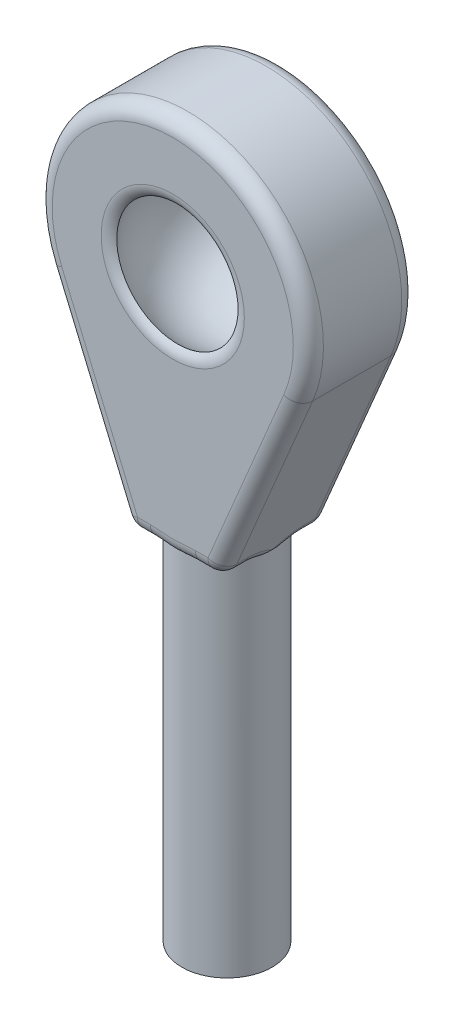
SolidWorks part; units mm, degrees
ref_plane "Front Plane" through (0, 0, 0) normal (0, 0, 1) x (1, 0, 0)
ref_plane "Top Plane" through (0, 0, 0) normal (0, 1, 0) x (1, 0, 0)
ref_plane "Right Plane" through (0, 0, 0) normal (1, 0, 0) x (0, 0, -1)
sketch "Sketch1" plane through (0, 0, 0) normal (0, 1, 0) x (1, 0, 0)
  circle A0 centre (0, 0) radius 1.5
  dimension "D1" = 3
extrude "Boss-Extrude1" add sketch "Sketch1" along normal blind 12
cosmetic thread "Cosmetic Thread1" parameters "D2"=2
sketch "Sketch3" plane through (0, 0, 0) normal (1, 0, 0) x (0, 0, -1)
  line L1 (-2.2, 21.3856) -> (2.2, 21.3856) construction
  line L2 (-2.2, 21.3856) -> (-2.2, 18.6144) construction
  line L3 (-2.2, 18.6144) -> (2.2, 18.6144) construction
  line L4 (2.2, 21.3856) -> (2.2, 18.6144) construction
  line L5 (-2.2, 21.3856) -> (2.2, 18.6144) construction
  line L6 (-2.2, 18.6144) -> (2.2, 21.3856) construction
  circle A0 centre (0, 20) radius 2.6
  point P0 (0, 20)
  point P8 (-1.8, 21.8762)
  dimension "D2" = 5.2
  dimension "D1" = 4.4
  dimension "D3" = 20
  dimension "D4" = 1.8
sketch "Sketch2" plane through (0, 0, 0) normal (0, 0, 1) x (1, 0, 0)
  line L0 (1.5, 12) -> (4.144, 18.2457)
  line L1 (-1.5, 12) -> (1.5, 12)
  line L2 (-4.144, 18.2457) -> (-1.5, 12)
  circle A0 centre (0, 20) radius 4.5
  circle A1 centre (0, 20) radius 1.8762
  dimension "D2" = 9
  dimension "D1" = 20
extrude "Boss-Extrude2" add sketch "Sketch2" along normal mid plane 3.6 contours A0 A1 | A0 L2 L1 L0 region at (0, 14.2994, 0) region at (0, 15.6273, 0)
fillet "Fillet2" radius 0.5 14 edges at (2.822, 15.1229, -1.8) (-2.822, 15.1229, -1.8) (2.822, 15.1229, 1.8) (-2.822, 15.1229, 1.8) (0, 24.5, -1.8) (0, 24.5, 1.8) (1.8762, 20, -1.8) (1.8762, 20, 1.8) (1.5, 12, -0.9) (-1.5, 12, -0.9) (1.5, 12, 0.9) (0, 12, -1.8) (-1.5, 12, 0.9) (0, 12, 1.8)
sketch "Sketch4" plane through (0, 0, 0) normal (1, 0, 0) x (0, 0, -1)
  line L0 (0, 22.6) -> (0, 17.4) construction
  circle A0 centre (0, 20) radius 2.6
  circle A1 centre (0, 20) radius 2.6 construction
revolve "Cut-Revolve2" cut sketch "Sketch4" angle 360 about L0 region at (0, 20, 1.1035)
